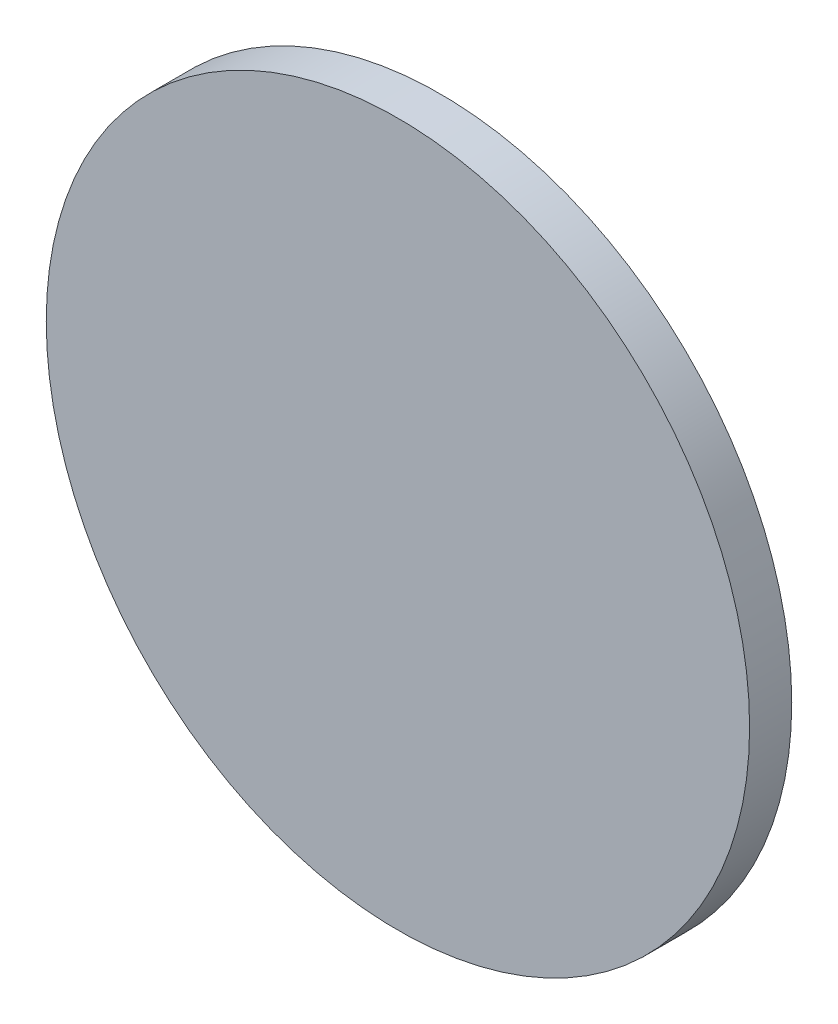
SolidWorks part; units mm, degrees
ref_plane "Alzado" through (0, 0, 0) normal (0, 0, 1) x (1, 0, 0)
ref_plane "Planta" through (0, 0, 0) normal (0, 1, 0) x (1, 0, 0)
ref_plane "Vista lateral" through (0, 0, 0) normal (1, 0, 0) x (0, 0, -1)
sketch "Croquis1" plane through (0, 0, 0) normal (1, 0, 0) x (0, 0, -1)
  line L0 (0, 52.5864) -> (0, -63.632)
  line L1 (0, -63.632) -> (13.927, -63.632)
  line L2 (13.927, -63.632) -> (13.927, 0)
  line L3 (13.927, 0) -> (35.0576, 52.5864)
  line L4 (35.0576, 52.5864) -> (0, 52.5864)
revolve "Revolución1" add sketch "Croquis1" angle 360 mid plane about L4
